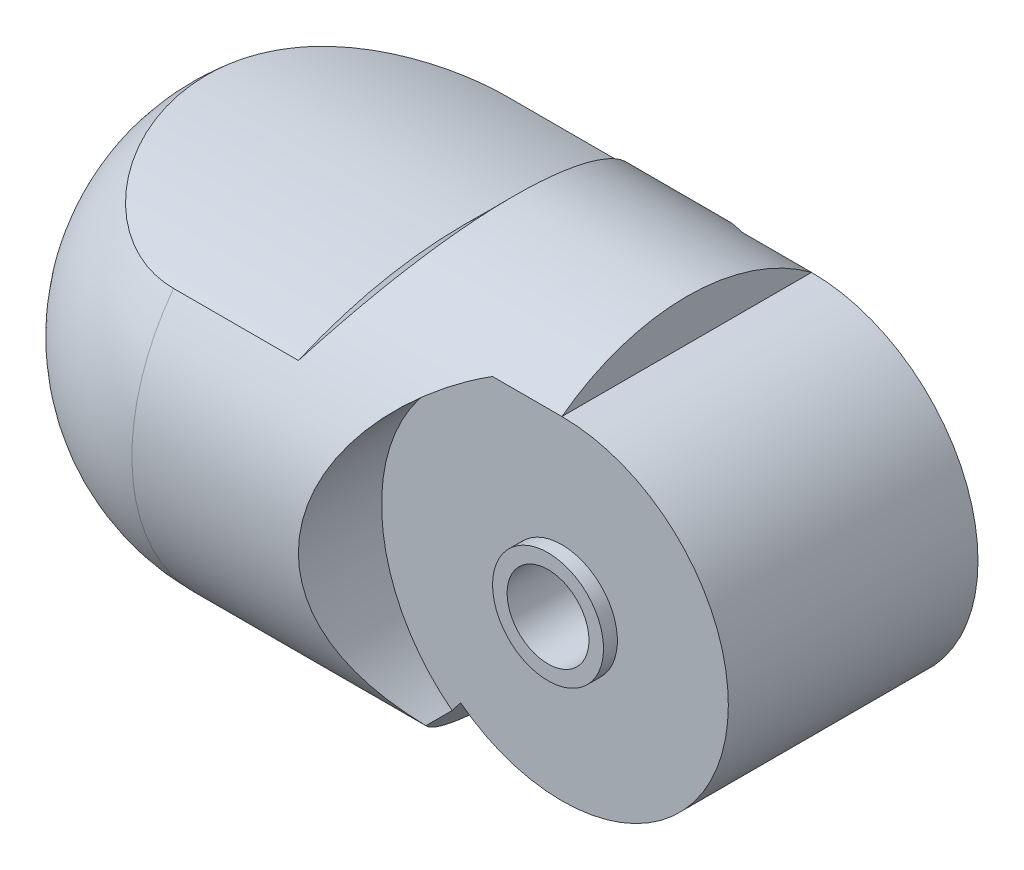
SolidWorks part; units mm, degrees
ref_plane "Front Plane" through (0, 0, 0) normal (0, 0, 1) x (1, 0, 0)
ref_plane "Top Plane" through (0, 0, 0) normal (0, 1, 0) x (1, 0, 0)
ref_plane "Right Plane" through (0, 0, 0) normal (1, 0, 0) x (0, 0, -1)
sketch "Sketch1" plane through (0, 0, 0) normal (0, 0, 1) x (1, 0, 0)
  circle A0 centre (0, 0) radius 1.475
  circle A1 centre (0, 0) radius 6
  dimension "D1" = 2.95
  dimension "D2" = 12
extrude "Boss-Extrude1" add sketch "Sketch1" along normal mid plane 9
sketch "Sketch5" plane through (0, 0, 0) normal (0, 0, 1) x (1, 0, 0)
  line L0 (-26.6252, 0) -> (14.5008, 0) construction
  line L1 (0, -7.5) -> (-12.5, -7.5)
  line L3 (0, 0) -> (0, -7.5)
  line L4 (-20, 0) -> (0, 0)
  arc A0 (-12.5, -7.5) -> (-20, 0) centre (-12.5, 0) cw
  dimension "D1" = 15
  dimension "D2" = 20
revolve "Revolve1" add sketch "Sketch5" angle 360 about L0
sketch "Sketch7" plane through (0, 0, 0) normal (0, 0, 1) x (1, 0, 0)
  line L0 (-3.6526, -4.7601) -> (-5.755, -7.5)
  line L1 (-12.5, -7.5) -> (0, -7.5) construction
  line L2 (-5.755, -7.5) -> (0, -7.5)
  line L3 (0, -7.5) -> (0, -6)
  arc A0 (0, -6) -> (-3.6526, -4.7601) centre (0, 0) ccw
  circle A1 centre (0, 0) radius 6 construction
  dimension "D2" = 6
  dimension "D1" = 37.5
extrude "Cut-Extrude2" cut sketch "Sketch7" against normal through all both and the other way through all
combine bodies "Combine1" operation type add bodies to combine 101 105
sketch "Sketch6" plane through (0, 0, 0) normal (1, 0, 0) x (0, 0, -1)
  arc A0 (-6, 4.5) -> (6, 4.5) centre (0, -9.2477) cw
  circle A1 centre (0, 0) radius 7.5 construction
  arc A2 (-6, 4.5) -> (6, 4.5) centre (0, 0) cw
  point P3 (0, 5.7523)
  dimension "D2" = 15
  dimension "D1" = 12
extrude "Cut-Extrude1" cut sketch "Sketch6" against normal through all from offset 6 offset against normal yes
chamfer "Chamfer1" distance 2 angle 45 1 edges at (-6, 5.7523, 0)
sketch "Sketch9" plane through (0, 0, 0) normal (0, 0, 1) x (1, 0, 0)
  circle A0 centre (0, 0) radius 6.5
  circle A1 centre (0, 0) radius 6 construction
  dimension "D1" = 0.5
extrude "Cut-Extrude3" cut sketch "Sketch9" along normal through all from surface starting at face at (0, 0, 4.5)
extrude "Cut-Extrude4" cut sketch "Sketch9<2>" against normal through all from surface starting at face at (0, 0, -4.5)
sketch "Sketch9<2>" plane through (0, 0, 0) normal (0, 0, 1) x (1, 0, 0) same geometry as "Sketch9"
sketch "Sketch10" plane through (0, 0, 0) normal (0, 1, 0) x (1, 0, 0)
  line L0 (6, 4.5) -> (-3.6526, 4.5) construction
  line L1 (1.475, 4.5) -> (2, 4.5)
  line L2 (1.475, 4.5) -> (1.475, 5)
  line L3 (1.475, 5) -> (2, 5)
  line L4 (2, 4.5) -> (2, 5)
  line L5 (1.475, 4.5) -> (-1.475, 4.5) construction
  line L6 (-3.6526, -4.5) -> (6, -4.5) construction
  line L7 (1.475, -4.5) -> (2, -4.5)
  line L8 (1.475, -4.5) -> (1.475, -5)
  line L9 (1.475, -5) -> (2, -5)
  line L10 (2, -4.5) -> (2, -5)
  line L11 (6, 0) -> (0, 0) construction
  line L12 (0, 4.5) -> (0, -4.5) construction
  line L13 (6, -4.5) -> (6, 4.5) construction
  dimension "D2" = 4
  dimension "D3" = 10
  dimension "D4" = 10
revolve "Revolve2" add sketch "Sketch10" angle 360 about L12
ref_axis "Axis1" through (0, 0, 5) along (0, 0, -1)
